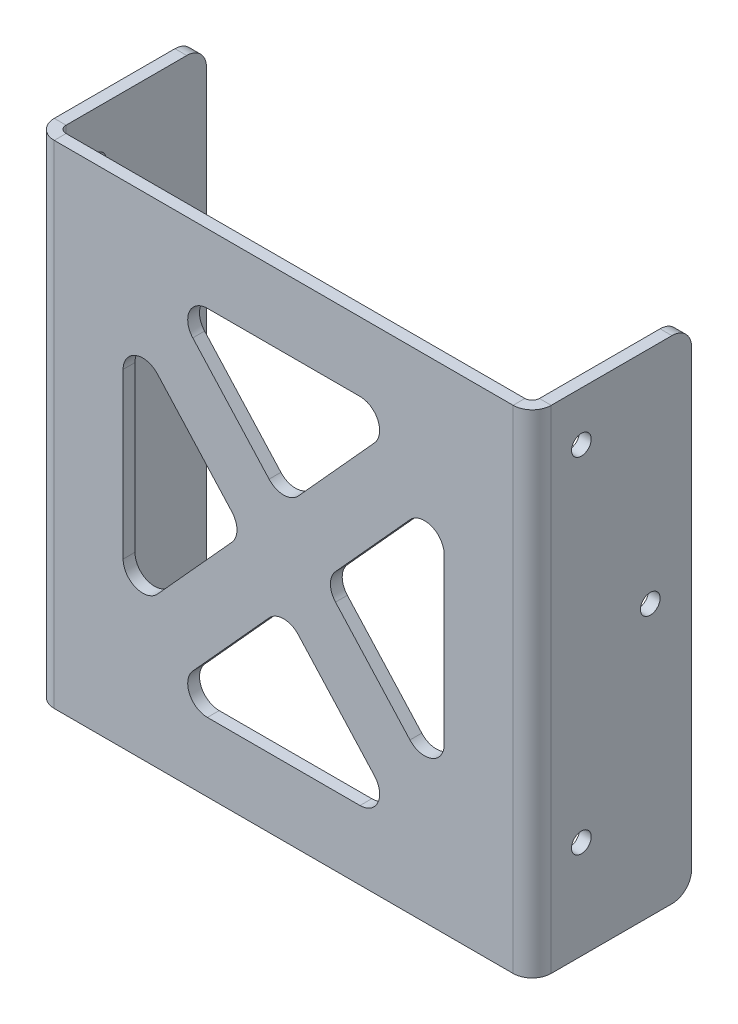
SolidWorks part; units mm, degrees
note: The reader was unsure of these and kept them because the rebuilt part matched: flange length of "邊線-凸緣1".
ref_plane "前基準面" through (0, 0, 0) normal (0, 0, 1) x (1, 0, 0)
ref_plane "上基準面" through (0, 0, 0) normal (0, 1, 0) x (1, 0, 0)
ref_plane "右基準面" through (0, 0, 0) normal (1, 0, 0) x (0, 0, -1)
sketch "草圖1" plane through (0, 0, 0) normal (0, 0, 1) x (1, 0, 0)
  line L1 (-24.05, 25) -> (24.05, 25)
  line L2 (-24.05, 25) -> (-24.05, -25)
  line L3 (-24.05, -25) -> (24.05, -25)
  line L4 (24.05, 25) -> (24.05, -25)
  line L5 (-24.05, 25) -> (24.05, -25) construction
  line L6 (-24.05, -25) -> (24.05, 25) construction
  point P0 (0, 0)
  dimension "D1" = 48.1
  dimension "D2" = 50
base flange "基材-凸緣1" sketch "草圖1" thickness 1.2 reverse thickness direction no parameters "D1"=0.7366
edge flange "邊線-凸緣1" sketch "草圖10" flange profiles "草圖10", "草圖11" flange angle 90 flange length 15 flange position material outside bend radius 0.7366 thickness 1.2 relief rectangular parameters "D6"=10, "D8"=1
sketch "草圖10" plane through (24.05, 0, -1.2) normal (-1, 0, 0) x (0, 1, 0)
  line L1 (25, 0) -> (-25, 0) construction
  line L2 (-25, 0) -> (-25, 15)
  line L3 (-25, 15) -> (25, 15)
  line L4 (25, 15) -> (25, 0)
  line L5 (25, 0) -> (-25, 0)
sketch "草圖11" plane through (-24.05, 0, -1.2) normal (1, 0, 0) x (0, -1, 0)
  line L0 (25, 0) -> (-25, 0) construction
  line L1 (25, 0) -> (-25, 0)
  line L2 (25, 0) -> (25, 15)
  line L3 (25, 15) -> (-25, 15)
  line L4 (-25, 15) -> (-25, 0)
bend "邊線彎折1" bend radius 0.7366 bend angle 90 parameters "D5"=1
bend "邊線彎折2" bend radius 0.7366 bend angle 90 parameters "D5"=2
sketch "草圖14" plane through (0, 0, 0) normal (0, 0, 1) x (1, 0, 0)
  line L0 (23.3134, 25) -> (-23.3134, 25) construction
  line L1 (23.3134, -25) -> (23.3134, 25) construction
  line L2 (-7.7529, 18) -> (7.7529, 18)
  line L3 (-16.3134, 8.3476) -> (-16.3134, -8.3476)
  line L4 (-7.7529, -18) -> (7.7529, -18)
  line L5 (16.3134, 8.3476) -> (16.3134, -8.3476)
  line L6 (5.266, -1.3431) -> (12.8315, -9.6907)
  line L7 (-12.8315, 9.6907) -> (-5.266, 1.3431)
  line L8 (5.266, 1.3431) -> (12.8315, 9.6907)
  line L9 (-9.2348, -14.6569) -> (-1.4819, -6.1025)
  line L10 (-9.2348, 14.6569) -> (-1.4819, 6.1025)
  line L11 (-12.8315, -9.6907) -> (-5.266, -1.3431)
  line L12 (1.4819, 6.1025) -> (9.2348, 14.6569)
  line L13 (1.4819, -6.1025) -> (9.2348, -14.6569)
  arc A0 (16.3134, -8.3476) -> (12.8315, -9.6907) centre (14.3134, -8.3476) cw
  arc A1 (5.266, -1.3431) -> (5.266, 1.3431) centre (6.7479, 0) cw
  arc A2 (16.3134, 8.3476) -> (12.8315, 9.6907) centre (14.3134, 8.3476) ccw
  arc A3 (9.2348, 14.6569) -> (7.7529, 18) centre (7.7529, 16) ccw
  arc A4 (1.4819, 6.1025) -> (-1.4819, 6.1025) centre (0, 7.4456) cw
  arc A5 (1.4819, -6.1025) -> (-1.4819, -6.1025) centre (0, -7.4456) ccw
  arc A6 (7.7529, -18) -> (9.2348, -14.6569) centre (7.7529, -16) ccw
  arc A7 (-9.2348, -14.6569) -> (-7.7529, -18) centre (-7.7529, -16) ccw
  arc A8 (-16.3134, -8.3476) -> (-12.8315, -9.6907) centre (-14.3134, -8.3476) ccw
  arc A9 (-5.266, -1.3431) -> (-5.266, 1.3431) centre (-6.7479, 0) ccw
  arc A10 (-12.8315, 9.6907) -> (-16.3134, 8.3476) centre (-14.3134, 8.3476) ccw
  arc A11 (-7.7529, 18) -> (-9.2348, 14.6569) centre (-7.7529, 16) ccw
  point P0 (0, 0)
  point P1 (17.5134, -33)
  point P2 (-17.5134, 33)
  point P3 (-17.5134, -33)
  point P4 (17.5134, 33)
  point P5 (-18.5363, 15.9854)
  point P9 (16.3134, -18)
  point P10 (-16.3134, 18)
  point P11 (-20.605, 31.3593)
  point P12 (14.4218, -34.6407)
  point P13 (-14.4218, -34.6407)
  point P14 (20.605, 31.3593)
  point P15 (-14.4218, 34.6407)
  point P16 (20.605, -31.3593)
  point P17 (-20.605, -31.3593)
  point P18 (14.4218, 34.6407)
  point P19 (-16.3134, -18)
  point P20 (16.3134, 18)
  point P23 (14.0905, -20.0146)
  point P24 (-14.0905, -20.0146)
  point P25 (18.5363, 15.9854)
  point P26 (-14.0905, 20.0146)
  point P27 (18.5363, -15.9854)
  point P28 (-18.5363, -15.9854)
  point P29 (14.0905, 20.0146)
  point P46 (4.0488, 0)
  dimension "D3" = 2
  dimension "D1" = 7
  dimension "D2" = 7
extrude "除料-伸長1" cut sketch "草圖14" against normal blind 10 normal cut yes
sketch "草圖17" plane through (25.25, 0, 0) normal (1, 0, 0) x (0, 0, -1)
  line L1 (1.9366, 25) -> (16.2, 25) construction
  line L3 (0, -25) -> (0, 25) construction
  circle A0 centre (5, 20) radius 1
  circle A1 centre (5, -15) radius 1
  circle A2 centre (12, 2.5) radius 1
  dimension "D1" = 2
  dimension "D4" = 2
  dimension "D7" = 2
  dimension "D2" = 5
  dimension "D3" = 35
  dimension "D5" = 5
  dimension "D6" = 5
  dimension "D8" = 7
  dimension "D9" = 17.5
extrude "除料-伸長2" cut sketch "草圖17" against normal through all normal cut yes
fillet "圓角1" radius 2 4 edges at (24.65, -25, -16.2) (-24.65, -25, -16.2) (-24.65, 25, -16.2) (24.65, 25, -16.2)
sketch "彎折-線1" plane through (0, 0, 0) normal (0, 1, 0) x (1, 0, 0)
sketch "邊界方塊1" plane through (0, 0, 0) normal (0, 1, 0) x (1, 0, 0)
sheet metal parameters "鈑金(1)" thickness 1.2 parameters "D1"=0.7366
flat pattern "平板-型式(1)" [suppressed]
sketch "彎折-線2" plane through (0, 0, 0) normal (0, 1, 0) x (1, 0, 0)
sketch "邊界方塊2" [suppressed] plane through (0, 0, 0) normal (0, 1, 0) x (1, 0, 0)
sheet metal parameters "鈑金(2)" thickness 1.2 parameters "D1"=0.7366
flat pattern "平板-型式(1)" [suppressed]
sketch "彎折-線3" plane through (0, 0, 0) normal (0, 1, 0) x (1, 0, 0)
sketch "邊界方塊3" [suppressed] plane through (0, 0, 0) normal (0, 1, 0) x (1, 0, 0)
bend of the flat pattern "平板-<邊線彎折1>1"
bend of the flat pattern "平板-<邊線彎折2>1"
sheet metal parameters "鈑金(3)" thickness 1.2 parameters "D1"=0.7366
flat pattern "平板-型式(1)" [suppressed]
sketch "彎折-線4" plane through (0, 0, 0) normal (0, 1, 0) x (1, 0, 0)
sketch "邊界方塊4" [suppressed] plane through (0, 0, 0) normal (0, 1, 0) x (1, 0, 0)
bend of the flat pattern "平板-<邊線彎折1>2"
bend of the flat pattern "平板-<邊線彎折2>2"
sheet metal parameters "鈑金(4)" thickness 1.2 parameters "D1"=0.7366
flat pattern "平板-型式(1)" [suppressed]
sketch "彎折-線5" plane through (0, 0, 0) normal (0, 1, 0) x (1, 0, 0)
sketch "邊界方塊5" [suppressed] plane through (0, 0, 0) normal (0, 1, 0) x (1, 0, 0)
bend of the flat pattern "平板-<邊線彎折1>3"
bend of the flat pattern "平板-<邊線彎折2>3"
